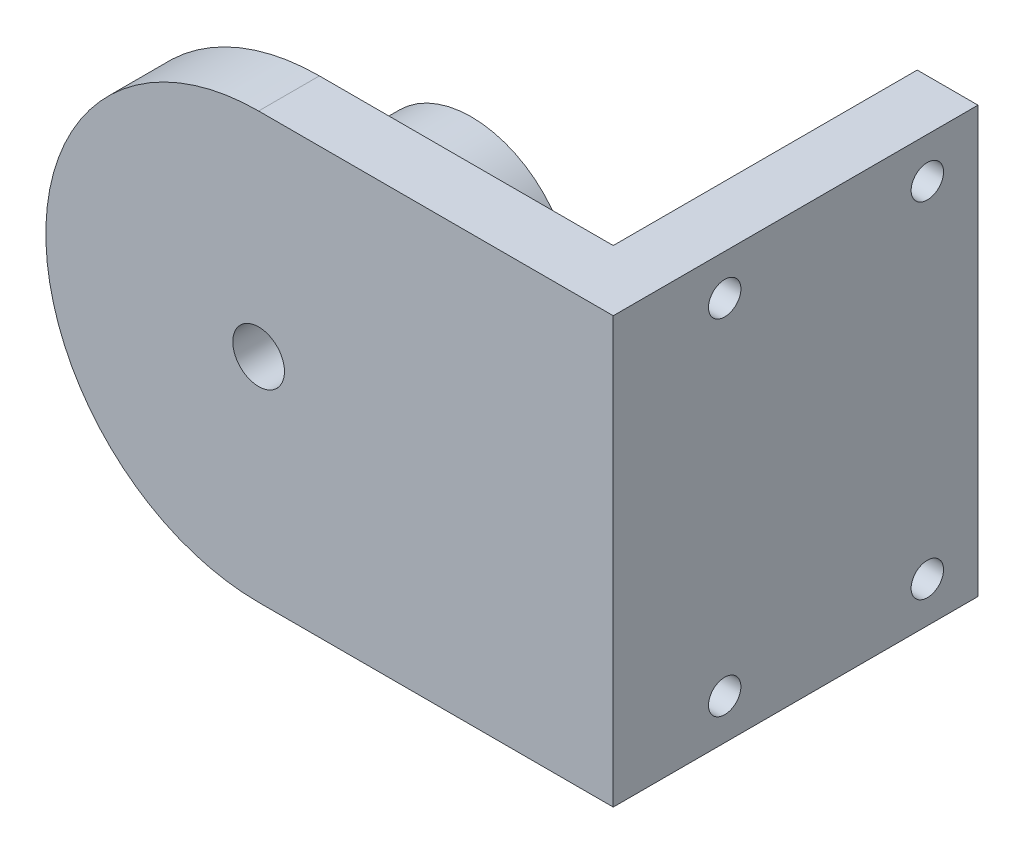
SolidWorks part; units mm, degrees
ref_plane "前视基准面" through (0, 0, 0) normal (0, 0, 1) x (1, 0, 0)
ref_plane "上视基准面" through (0, 0, 0) normal (0, 1, 0) x (1, 0, 0)
ref_plane "右视基准面" through (0, 0, 0) normal (1, 0, 0) x (0, 0, -1)
sketch "草图1" plane through (0, 0, 0) normal (0, 0, 1) x (1, 0, 0)
  circle A0 centre (-2.1417, 2.0638) radius 10
  circle A1 centre (-2.1417, 2.0638) radius 2.55
  dimension "D1" = 20
  dimension "D2" = 5.1
extrude "凸台-拉伸1" add sketch "草图1" along normal blind 15
sketch "草图2" plane through (0, 0, 15) normal (0, 0, 1) x (1, 0, 0)
  line L0 (-12.1417, 2.0638) -> (7.8583, 2.0638)
  circle A0 centre (-2.1417, 2.0638) radius 10 construction
ref_plane "基准面1" through (7.8583, 0, 0) normal (1, 0, 0) x (0, 0, -1)
sketch "草图3" plane through (7.8583, 0, 0) normal (1, 0, 0) x (0, 0, -1)
  line L0 (-15, 2.0638) -> (0, 2.0638) construction
  line L1 (-15, 12.0638) -> (-15, -7.9362) construction
  line L2 (0, -7.9362) -> (0, 12.0638) construction
  circle A0 centre (-7.5, 2.0638) radius 1.6
  dimension "D1" = 3.2
extrude "切除-拉伸1" cut sketch "草图3" against normal through all
sketch "草图5" plane through (0, 0, 15) normal (0, 0, 1) x (1, 0, 0)
  line L0 (7.8583, -8.25) -> (7.8583, 8.25) construction
  line L1 (-2.1417, 23.0638) -> (32.8583, 23.0638)
  line L3 (-2.1417, -18.9362) -> (32.8583, -18.9362)
  line L4 (32.8583, 23.0638) -> (32.8583, -18.9362)
  arc A0 (-2.1417, 23.0638) -> (-2.1417, -18.9362) centre (-2.1417, 2.0638) ccw
  dimension "D1" = 21
  dimension "D2" = 25
extrude "凸台-拉伸2" add sketch "草图5" along normal blind 6
sketch "草图6" plane through (0, 0, 15) normal (0, 0, -1) x (-1, 0, 0)
  line L0 (12.1417, 2.0638) -> (-7.8583, 2.0638) construction
  circle A0 centre (2.1417, 2.0638) radius 2.55
  circle A1 centre (2.1417, 2.0638) radius 2.55 construction
extrude "切除-拉伸2" cut sketch "草图6" against normal blind 10
sketch "草图7" plane through (32.8583, 0, 0) normal (1, 0, 0) x (0, 0, -1)
  line L0 (-21, -18.9362) -> (-15, -18.9362) construction
  line L1 (-15, 23.0638) -> (15, 23.0638)
  line L2 (-15, 23.0638) -> (-15, -18.9362)
  line L3 (-15, -18.9362) -> (15, -18.9362)
  line L4 (15, 23.0638) -> (15, -18.9362)
  dimension "D1" = 30
extrude "凸台-拉伸3" add sketch "草图7" against normal blind 6
sketch "草图8" plane through (32.8583, 0, 0) normal (1, 0, 0) x (0, 0, -1)
  line L0 (-21, 23.0638) -> (15, 23.0638) construction
  line L1 (-10, 19.0638) -> (10, 19.0638) construction
  line L2 (-10, 19.0638) -> (-10, -14.9362) construction
  line L3 (-10, -14.9362) -> (10, -14.9362) construction
  line L4 (10, 19.0638) -> (10, -14.9362) construction
  line L6 (15, -18.9362) -> (15, 23.0638) construction
  circle A0 centre (-10, 19.0638) radius 1.6
  circle A1 centre (-10, -14.9362) radius 1.6
  circle A2 centre (10, -14.9362) radius 1.6
  circle A3 centre (10, 19.0638) radius 1.6
  dimension "D5" = 3.2
  dimension "D1" = 4
  dimension "D2" = 34
  dimension "D3" = 5
  dimension "D4" = 20
extrude "切除-拉伸3" cut sketch "草图8" against normal blind 6
